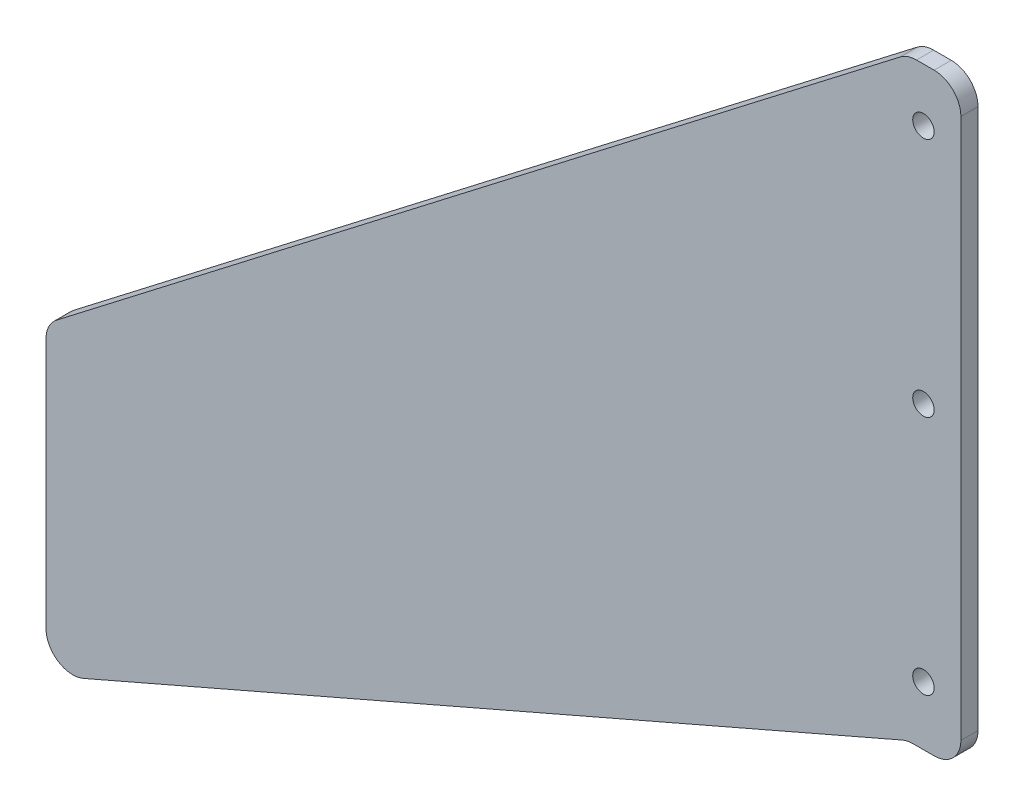
SolidWorks part; units mm, degrees
ref_plane "Спереди" through (0, 0, 0) normal (0, 0, 1) x (1, 0, 0)
ref_plane "Сверху" through (0, 0, 0) normal (0, 1, 0) x (1, 0, 0)
ref_plane "Справа" through (0, 0, 0) normal (1, 0, 0) x (0, 0, -1)
sketch "Эскиз1" plane through (0, 0, 0) normal (0, 0, 1) x (1, 0, 0)
  line L12 (-4.3486, 8.9613) -> (-162.0509, -112.4989)
  line L13 (-164, -116.4601) -> (-164, -163.3739)
  line L14 (-157.0064, -167.9593) -> (-3.9537, -101.4146)
  line L15 (-1.9601, -101) -> (2, -101)
  line L16 (7, -96) -> (7, 5)
  line L17 (2, 10) -> (-1.2977, 10)
  arc A1 (1.2036, -1.5973) -> (-1.2036, 1.5973) centre (0, 0) ccw
  arc A3 (-1.2036, 1.5973) -> (1.2036, -1.5973) centre (0, 0) ccw
  arc A14 (-1.2977, 10) -> (-4.3486, 8.9613) centre (-1.2977, 5) ccw
  arc A15 (-162.0509, -112.4989) -> (-164, -116.4601) centre (-159, -116.4601) ccw
  arc A16 (-164, -163.3739) -> (-157.0064, -167.9593) centre (-159, -163.3739) ccw
  arc A17 (-1.9601, -101) -> (-3.9537, -101.4146) centre (-1.9601, -106) ccw
  arc A18 (2, -101) -> (5.0091, -99.9932) centre (2, -96) ccw
  arc A19 (5.0091, -99.9932) -> (7, -96) centre (2, -96) ccw
  arc A20 (7, 5) -> (2, 10) centre (2, 5) ccw
  arc A22 (1.2036, -46.5973) -> (-1.2036, -43.4027) centre (0, -45) ccw
  arc A23 (-1.2036, -43.4027) -> (1.2036, -46.5973) centre (0, -45) ccw
  arc A26 (1.2036, -91.5973) -> (-1.2036, -88.4027) centre (0, -90) ccw
  arc A27 (-1.2036, -88.4027) -> (1.2036, -91.5973) centre (0, -90) ccw
extrude "Бобышка-Вытянуть1" add sketch "Эскиз1" against normal blind 1.6 and the other way blind 1.6
